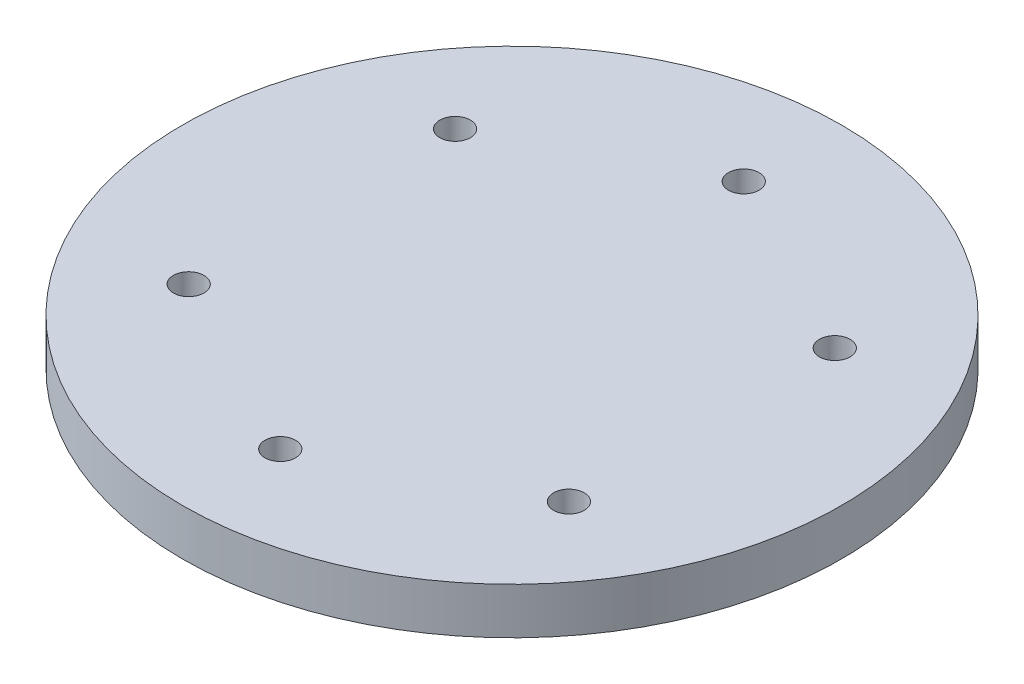
SolidWorks part; units mm, degrees
ref_plane "Front Plane" through (0, 0, 0) normal (0, 0, 1) x (1, 0, 0)
ref_plane "Top Plane" through (0, 0, 0) normal (0, 1, 0) x (1, 0, 0)
ref_plane "Right Plane" through (0, 0, 0) normal (1, 0, 0) x (0, 0, -1)
sketch "Sketch1" plane through (0, 0, 0) normal (0, 1, 0) x (1, 0, 0)
  circle A0 centre (0, 0) radius 35.55
  dimension "D1" = 71.1
extrude "Boss-Extrude1" add sketch "Sketch1" along normal blind 5
sketch "Sketch2" plane through (0, 5, 0) normal (0, 1, 0) x (1, 0, 0)
  line L0 (0, 0) -> (-35.55, 0) construction
  line L1 (0, 0) -> (-29.1209, 20.3906) construction
  line L2 (0, 0) -> (29.1209, 20.3906) construction
  line L3 (0, 35.55) -> (0, -35.55) construction
  line L4 (0, 0) -> (-29.1209, -20.3906) construction
  line L5 (0, 0) -> (29.1209, -20.3906) construction
  line L6 (0, 0) -> (35.55, 0) construction
  circle A0 centre (0, 0) radius 35.55 construction
  circle A2 centre (0, 25) radius 1.65
  circle A3 centre (-20.4788, 14.3394) radius 1.65
  circle A4 centre (20.4788, 14.3394) radius 1.65
  circle A5 centre (20.4788, -14.3394) radius 1.65
  circle A6 centre (0, -25) radius 1.65
  circle A7 centre (-20.3387, -14.5375) radius 1.65
  dimension "D2" = 25
  dimension "D3" = 3.3
  dimension "D1" = 35
  dimension "D4" = 35
  dimension "D5" = 35
  dimension "D6" = 35
  dimension "D7" = 55
extrude "Cut-Extrude1" cut sketch "Sketch2" against normal blind 10
